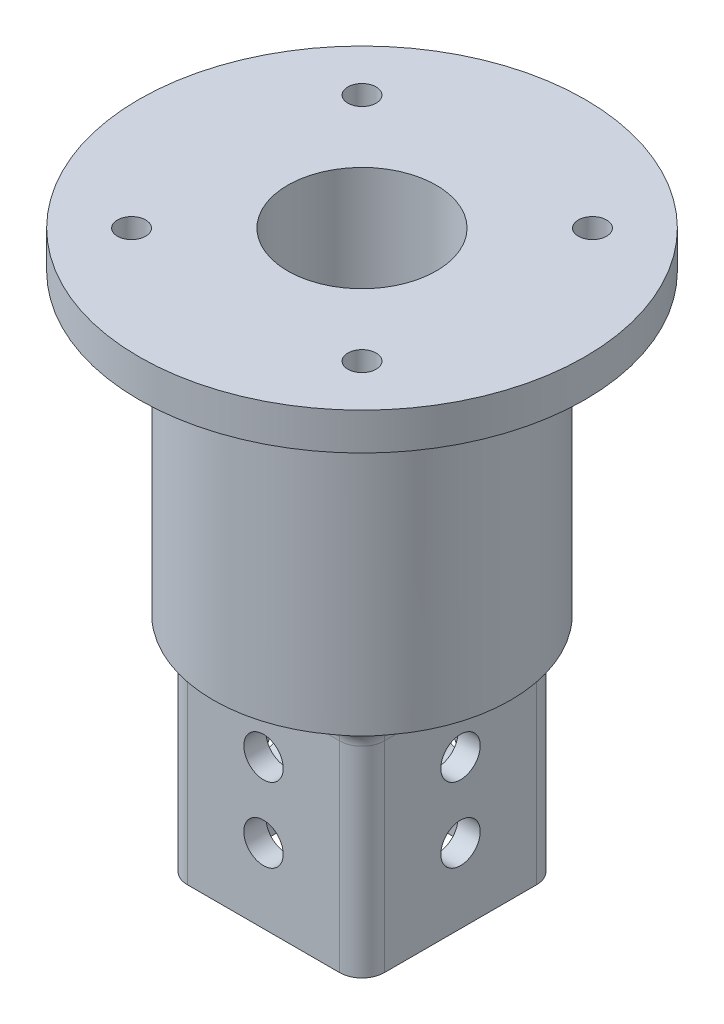
SolidWorks part; units mm, degrees
ref_plane "前视基准面" through (0, 0, 0) normal (0, 0, 1) x (1, 0, 0)
ref_plane "上视基准面" through (0, 0, 0) normal (0, 1, 0) x (1, 0, 0)
ref_plane "右视基准面" through (0, 0, 0) normal (1, 0, 0) x (0, 0, -1)
other "Configuration Table"
sketch "草图1" plane through (0, 0, 0) normal (0, 1, 0) x (1, 0, 0)
  line L1 (-10.25, -10.25) -> (10.25, -10.25)
  line L2 (-10.25, -10.25) -> (-10.25, 10.25)
  line L3 (-10.25, 10.25) -> (10.25, 10.25)
  line L4 (10.25, -10.25) -> (10.25, 10.25)
  line L5 (-10.25, -10.25) -> (10.25, 10.25) construction
  line L6 (-10.25, 10.25) -> (10.25, -10.25) construction
  circle A0 centre (0, 0) radius 20
  dimension "D1" = 40
  dimension "D2" = 20.5
  dimension "D3" = 20.5
extrude "凸台-拉伸1" add sketch "草图1" along normal blind 30
sketch "草图3" plane through (0, 0, 0) normal (0, -1, 0) x (1, 0, 0)
  line L11 (-10.25, 10.25) -> (10.25, 10.25)
  line L12 (-10.25, 10.25) -> (-10.25, -10.25)
  line L13 (-10.25, -10.25) -> (10.25, -10.25)
  line L14 (13.25, -13.25) -> (13.25, 13.25)
  line L15 (-13.25, -13.25) -> (13.25, -13.25)
  line L16 (-13.25, 13.25) -> (-13.25, -13.25)
  line L17 (13.25, 13.25) -> (-13.25, 13.25)
  line L18 (13.25, -13.25) -> (13.25, 13.25)
  line L19 (-13.25, -13.25) -> (13.25, -13.25)
  line L20 (-13.25, 13.25) -> (-13.25, -13.25)
  line L21 (13.25, 13.25) -> (-13.25, 13.25)
  line L22 (10.25, 10.25) -> (10.25, -10.25)
  dimension "D1" = 3
sketch "草图5" plane through (0, 30, 0) normal (0, 1, 0) x (1, 0, 0)
  circle A0 centre (0, 0) radius 20
extrude "凸台-拉伸3" add sketch "草图5" along normal blind 10
extrude "凸台-拉伸4" add sketch "草图3" along normal blind 30
sketch "草图6" plane through (0, 0, 13.25) normal (0, 0, 1) x (1, 0, 0)
  line L0 (0, 0) -> (0, -10)
  line L1 (0, -10) -> (0, -20)
  circle A0 centre (0, -10) radius 2.15
  circle A1 centre (0, -20) radius 2.15
  dimension "D2" = 4.3
  dimension "D4" = 4.3
  dimension "D1" = 10
  dimension "D3" = 10
extrude "切除-拉伸1" cut sketch "草图6" against normal blind 30 contours A0 | A1
sketch "草图7" plane through (-13.25, 0, 0) normal (-1, 0, 0) x (0, 0, 1)
  line L0 (0, -1000) -> (0, 49000) construction
  circle A0 centre (0, -10) radius 2.15
  circle A1 centre (0, -20) radius 2.15
  dimension "D3" = 4.3
  dimension "D4" = 4.3
  dimension "D1" = 10
  dimension "D2" = 10
extrude "切除-拉伸2" cut sketch "草图7" against normal blind 30
fillet "圆角1" radius 3 1 edges at (-13.25, -15, 13.25) type face fillet first side face at (-13.25, -10, 2.15) second side face at (2.15, -10, 13.25)
fillet "圆角2" radius 3 1 edges at (13.25, -15, 13.25) type face fillet first side face at (2.15, -10, 13.25) second side face at (13.25, -10, 2.15)
fillet "圆角3" radius 3 1 edges at (13.25, -15, -13.25) type face fillet first side face at (13.25, -10, 2.15) second side face at (2.15, -10, -13.25)
fillet "圆角4" radius 3 1 edges at (-13.25, -15, -13.25) type face fillet first side face at (2.15, -10, -13.25) second side face at (-13.25, -10, 2.15)
fillet "圆角5" radius 3 8 edges at (-12.3713, 0, -12.3713) (12.3713, 0, -12.3713) (12.3713, 0, 12.3713) (-12.3713, 0, 12.3713) (0, 0, -13.25) (-13.25, 0, 0) (0, 0, 13.25) (13.25, 0, 0) type face fillet first side face at (12.0607, -15, 12.0607) first side face at (-12.0607, -15, 12.0607) first side face at (-12.0607, -15, -12.0607) first side face at (12.0607, -15, -12.0607) first side face at (13.25, -10, 2.15) first side face at (2.15, -10, -13.25) first side face at (-13.25, -10, 2.15) first side face at (2.15, -10, 13.25) second side face at (0, 0, 20)
sketch "草图11" plane through (0, 40, 0) normal (0, 1, 0) x (1, 0, 0)
  circle A0 centre (0, 0) radius 30
  dimension "D1" = 60
extrude "凸台-拉伸5" add sketch "草图11" along normal blind 5
fillet "圆角6" radius 5 1 edges at (0, 40, 20) type face fillet first side face at (0, 40, 20) second side face at (0, 0, 0)
sketch "草图12" plane through (0, 45, 0) normal (0, 1, 0) x (1, 0, 0)
  line L5 (-15.5, -15.5) -> (15.5, 15.5) construction
  line L6 (-15.5, 15.5) -> (15.5, -15.5) construction
  circle A0 centre (-15.5, 15.5) radius 1.9
  circle A3 centre (15.5, 15.5) radius 1.9
  circle A4 centre (15.5, -15.5) radius 1.9
  circle A5 centre (-15.5, -15.5) radius 1.9
  circle A6 centre (0, 0) radius 10
  point P0 (0, 0)
  point P16 (0, 0)
  dimension "D3" = 3.8
  dimension "D5" = 20
  dimension "D1" = 31
  dimension "D2" = 31
  dimension "D4" = 4
extrude "切除-拉伸4" cut sketch "草图12" against normal through all
sketch "草图13" plane through (0, 0, -13.25) normal (0, 0, -1) x (-1, 0, 0)
  circle A0 centre (0, -10) radius 2.65
  circle A1 centre (0, -20) radius 2.65
  dimension "D1" = 5.3
  dimension "D2" = 5.3
extrude "切除-拉伸5" cut sketch "草图13" against normal through all
sketch "草图14" plane through (-13.25, 0, 0) normal (-1, 0, 0) x (0, 0, 1)
  circle A0 centre (0, -10) radius 2.65
  circle A1 centre (0, -20) radius 2.65
  dimension "D1" = 5.3
  dimension "D2" = 5.3
extrude "切除-拉伸6" cut sketch "草图14" against normal through all
